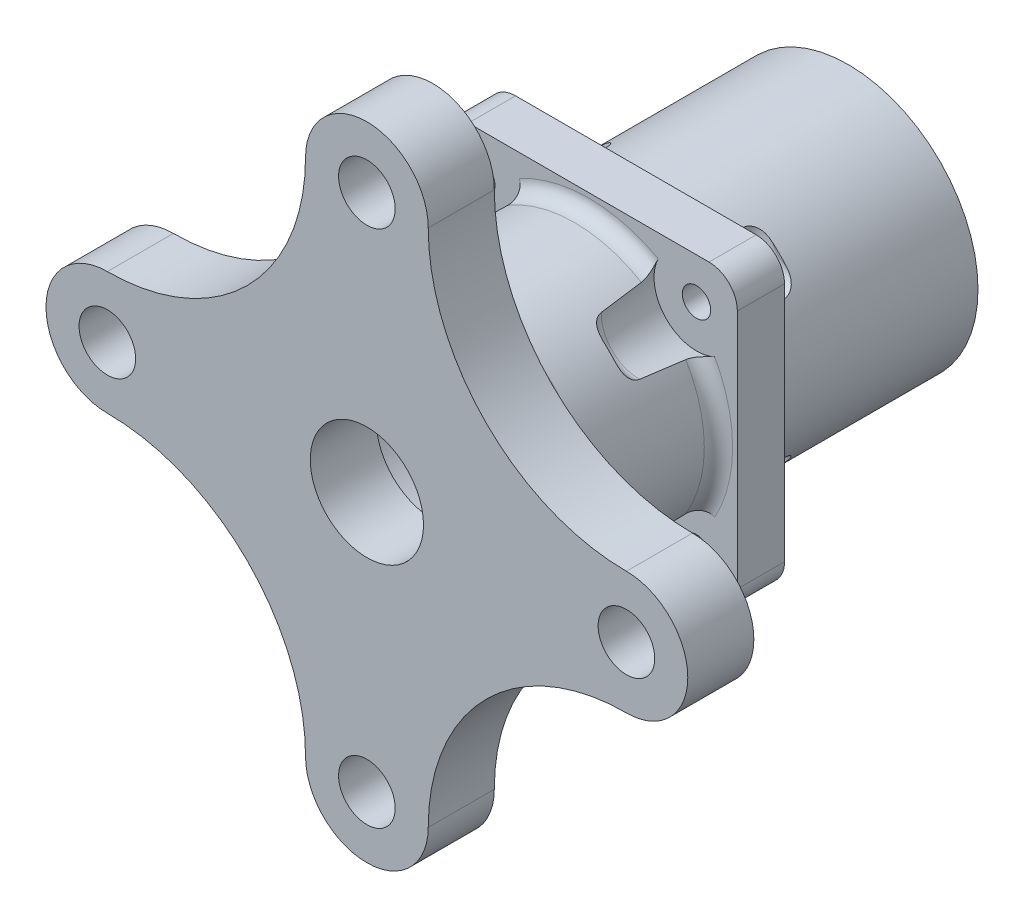
SolidWorks part; units mm, degrees
ref_plane "Front Plane" through (0, 0, 0) normal (0, 0, 1) x (1, 0, 0)
ref_plane "Top Plane" through (0, 0, 0) normal (0, 1, 0) x (1, 0, 0)
ref_plane "Right Plane" through (0, 0, 0) normal (1, 0, 0) x (0, 0, -1)
sketch "Sketch1" plane through (0, 0, 0) normal (0, 0, 1) x (1, 0, 0)
  circle A0 centre (0, 0) radius 20
  circle A1 centre (0, 0) radius 27.5
  dimension "D1" = 40
  dimension "D2" = 55
extrude "Boss-Extrude1" add sketch "Sketch1" along normal blind 88
ref_plane "Plane1" through (0, 0, 45) normal (0, 0, -1) x (-1, 0, 0)
sketch "Sketch2" plane through (0, 0, 45) normal (0, 0, -1) x (-1, 0, 0)
  line L0 (0, 0) -> (46.4229, 0) construction
  line L1 (-25.5, -31.5) -> (25.5, -31.5)
  line L2 (-31.5, -25.5) -> (-31.5, 25.5)
  line L3 (-25.5, 31.5) -> (25.5, 31.5)
  line L4 (31.5, -25.5) -> (31.5, 25.5)
  line L5 (-31.5, -31.5) -> (31.5, 31.5) construction
  line L6 (-31.5, 31.5) -> (31.5, -31.5) construction
  circle A0 centre (22.8466, 22.8466) radius 3
  circle A1 centre (-22.8466, -22.8466) radius 3
  circle A2 centre (22.8466, -22.8466) radius 3
  circle A3 centre (-22.8466, 22.8466) radius 3
  arc A4 (25.5, -31.5) -> (31.5, -25.5) centre (25.5, -25.5) ccw
  arc A5 (-25.5, -31.5) -> (-31.5, -25.5) centre (-25.5, -25.5) cw
  arc A6 (-31.5, 25.5) -> (-25.5, 31.5) centre (-25.5, 25.5) cw
  arc A7 (25.5, 31.5) -> (31.5, 25.5) centre (25.5, 25.5) cw
  circle A8 centre (0, 0) radius 27.5
  point P0 (0, 0)
  dimension "D3" = 6
  dimension "D4" = 6
  dimension "D1" = 63
  dimension "D2" = 63
  dimension "D5" = 32.31
extrude "Boss-Extrude2" add sketch "Sketch2" against normal blind 10
sketch "Sketch3" plane through (0, 0, 88) normal (0, 0, 1) x (1, 0, 0)
  line L0 (0, 42) -> (0, 55) construction
  line L1 (0, 0) -> (55, 0) construction
  line L2 (0, 55) -> (21.233, 55) construction
  line L3 (55, 0) -> (55, 23.4869) construction
  line L4 (13, 55) -> (13, 33.7853) construction
  line L5 (55, 13) -> (81.8117, 13) construction
  circle A0 centre (0, 0) radius 55 construction
  circle A1 centre (0, 55) radius 6
  circle A2 centre (55, 0) radius 6
  circle A3 centre (0, -55) radius 6
  circle A4 centre (-55, 0) radius 6
  arc A5 (12.9089, 53.4636) -> (-12.9089, 53.4636) centre (0, 55) ccw
  arc A6 (53.4636, -12.9089) -> (53.4636, 12.9089) centre (55, 0) ccw
  arc A7 (-12.9089, -53.4636) -> (12.9089, -53.4636) centre (0, -55) ccw
  arc A8 (-53.4636, 12.9089) -> (-53.4636, -12.9089) centre (-55, 0) ccw
  arc A9 (13, 55) -> (55, 13) centre (55, 55) ccw
  arc A10 (55, -13) -> (13, -55) centre (55, -55) ccw
  arc A11 (-13, -55) -> (-55, -13) centre (-55, -55) ccw
  arc A12 (-55, 13) -> (-13, 55) centre (-55, 55) ccw
  circle A13 centre (0, 0) radius 12
  point P10 (13, 55)
  point P15 (0, 0)
  point P16 (55, 13)
  point P23 (0, 0)
  point P41 (0, 0)
  circle M1 centre (0, 0) radius 27.5
  circle M2 centre (0, 0) radius 20
  dimension "D1" = 110
  dimension "D2" = 4
  dimension "D3" = 12
  dimension "D5" = 26
  dimension "D7" = 24
  dimension "D6" = 4
  dimension "D4" = 4
extrude "Boss-Extrude3" add sketch "Sketch3" along normal blind 14 contours A12 A8 A11 A7 A10 A6 A9 A5 A4 A3 A2 A1 M1 | M1 M2 | A13 M2 region at (23.9415, 23.9415, 88) region at (-26.7222, 0, 88) region at (-19.4343, 0, 88)
sketch "Sketch4" plane through (0, 0, 45) normal (0, 0, -1) x (-1, 0, 0)
  circle A0 centre (22.8466, 22.8466) radius 9
  circle A1 centre (22.8466, -22.8466) radius 9
  circle A2 centre (-22.8466, -22.8466) radius 9
  circle A3 centre (-22.8466, 22.8466) radius 9
  point P12 (0, 0)
  dimension "D2" = 18
  dimension "D1" = 4
extrude "Cut-Extrude1" cut sketch "Sketch4" along normal blind 11 draft 5
sketch "Sketch5" plane through (0, 0, 55) normal (0, 0, 1) x (1, 0, 0)
  circle A0 centre (22.8466, 22.8466) radius 9
  circle A1 centre (22.8466, -22.8466) radius 9
  circle A2 centre (-22.8466, -22.8466) radius 9
  circle A3 centre (-22.8466, 22.8466) radius 9
  point P12 (0, 0)
  dimension "D1" = 18
  dimension "D2" = 4
extrude "Cut-Extrude2" cut sketch "Sketch5" along normal blind 15 draft 5
fillet "Fillet1" radius 3 8 edges at (17.1632, 17.1632, 34) (-17.4106, -17.4106, 70) (17.4106, -17.4106, 70) (17.4106, 17.4106, 70) (-17.4106, 17.4106, 70) (-17.1632, 17.1632, 34) (-17.1632, -17.1632, 34) (17.1632, -17.1632, 34)
fillet "Fillet2" radius 3 8 edges at (0, 27.5, 55) (-27.5, 0, 55) (0, -27.5, 55) (27.5, 0, 55) (-27.5, 0, 45) (0, 27.5, 45) (0, -27.5, 45) (27.5, 0, 45)
fillet "Fillet3" radius 6 1 edges at (27.5, 0, 88)
